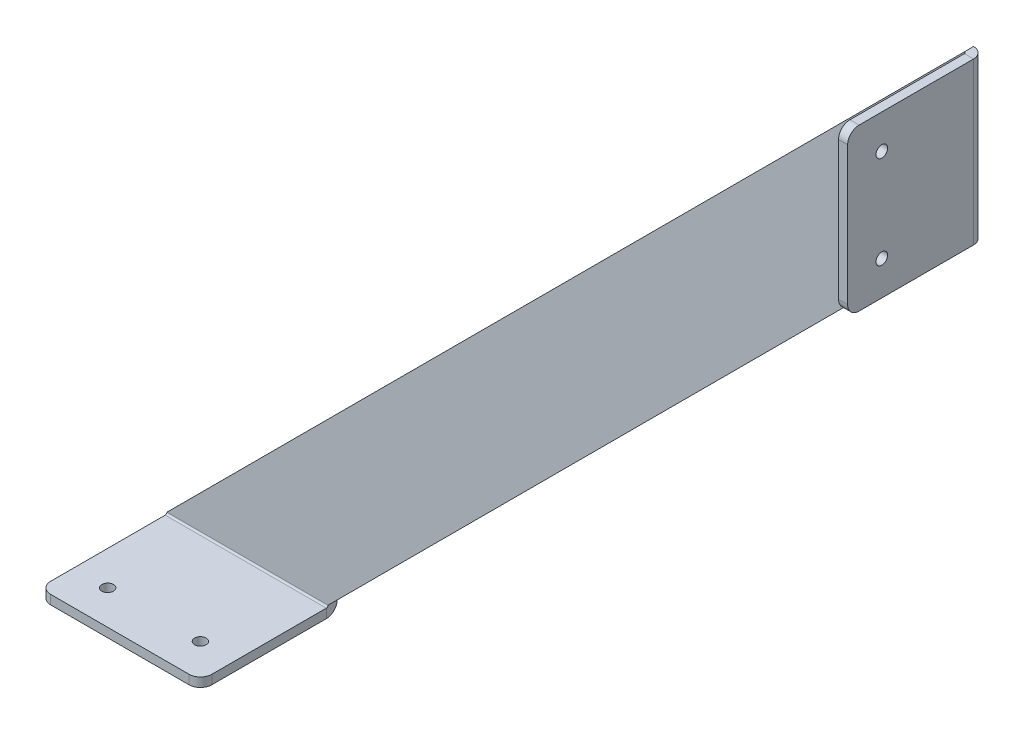
SolidWorks part; units mm, degrees
note: The reader was unsure of these and kept them because the rebuilt part matched: flange length of "Edge-Flange1".
material "AISI 304"
ref_plane "Front Plane" through (0, 0, 0) normal (0, 0, 1) x (1, 0, 0)
ref_plane "Top Plane" through (0, 0, 0) normal (0, 1, 0) x (1, 0, 0)
ref_plane "Right Plane" through (0, 0, 0) normal (1, 0, 0) x (0, 0, -1)
sketch "Sketch1" plane through (0, 0, 0) normal (0, 0, 1) x (1, 0, 0)
  line L0 (175, 175) -> (-175, -175)
  line L1 (-175, -175) -> (175, -175) construction
  line L2 (-175, -175) -> (-175, 175) construction
  line L3 (-175, 175) -> (175, 175) construction
  line L4 (175, -175) -> (175, 175) construction
  line L5 (-175, -175) -> (175, 175) construction
  line L6 (-175, 175) -> (175, -175) construction
  line L7 (-175, -175) -> (-104.2893, -175)
  line L8 (-104.2893, -175) -> (175, 104.2893)
  line L9 (175, 104.2893) -> (175, 175)
  point P0 (0, 0)
  dimension "Lateral" = 350
  dimension "D3" = 50
sheet metal parameters "Sheet-Metal1" thickness 4 parameters "D1"=0.7366
base flange "Base-Flange1" sketch "Sketch1" thickness 4 reverse thickness direction no parameters "D1"=0.7366
edge flange "Edge-Flange1" sketch "Sketch8" flange profiles "Sketch8", "Sketch9" flange angle 90 flange length 60 flange position bend outside bend radius 0.7366 thickness 4 parameters "D6"=10, "D8"=1
sketch "Sketch8" plane through (175, 0, 0) normal (1, 0, 0) x (0, 1, 0)
  line L2 (104.2893, 0) -> (104.2893, 56)
  line L3 (104.2893, 56) -> (175, 56)
  line L4 (175, 56) -> (175, 0)
  line L5 (104.2893, 0) -> (175, 0) construction
  line L6 (104.2893, 0) -> (175, 0)
sketch "Sketch9" plane through (0, -175, 0) normal (0, -1, 0) x (1, 0, 0)
  line L0 (-175, 0) -> (-104.2893, 0) construction
  line L1 (-175, 0) -> (-104.2893, 0)
  line L2 (-175, 0) -> (-175, 56)
  line L3 (-175, 56) -> (-104.2893, 56)
  line L4 (-104.2893, 56) -> (-104.2893, 0)
bend "EdgeBend1" bend radius 0.7366 bend angle 90 parameters "D5"=1
bend "EdgeBend2" bend radius 0.7366 bend angle 90 parameters "D5"=2
sketch "Sketch13" plane through (179.7366, 0, 0) normal (1, 0, 0) x (0, 0, -1)
  line L0 (4, 104.2893) -> (4, 175) construction
  line L4 (-0.7366, 175) -> (-56, 175) construction
  line L5 (-28, 175) -> (-28, 104.2893) construction
  line L6 (-56, 104.2893) -> (-0.7366, 104.2893) construction
  line L7 (-56, 175) -> (-56, 104.2893) construction
  line L10 (-41, 175) -> (-41, 104.2893) construction
  line L11 (-56, 139.6447) -> (27.4411, 139.6447) construction
  circle A0 centre (-41, 160) radius 2.55
  circle A1 centre (-41, 119.2893) radius 2.55
  dimension "D3" = 5.1
  dimension "D1" = 28
  dimension "D2" = 45
  dimension "D5" = 15
extrude "Cut-Extrude1" cut sketch "Sketch13" against normal up to surface (4 mm away) up to face at (175.7366, 139.6447, 28.3683)
sketch "Sketch14" plane through (0, -179.7366, 0) normal (0, -1, 0) x (1, 0, 0)
  line L0 (-104.2893, 41) -> (-175, 41) construction
  line L1 (-104.2893, 56) -> (-104.2893, 0) construction
  line L2 (-175, 56) -> (-175, 0.7366) construction
  line L3 (-104.2893, 56) -> (-175, 56) construction
  line L4 (-139.6447, 56) -> (-139.6447, -9.1129) construction
  line L5 (-104.2893, 0.7366) -> (-104.2893, 56) construction
  line L6 (-175, -4) -> (-104.2893, -4) construction
  circle A0 centre (-119.2893, 41) radius 2.55
  circle A1 centre (-160, 41) radius 2.55
  dimension "D2" = 5.1
  dimension "D3" = 15
  dimension "D1" = 45
extrude "Cut-Extrude2" cut sketch "Sketch14" against normal up to surface (4 mm away) up to face at (-139.6447, -175.7366, 28.3683)
fillet "Fillet1" radius 5 4 edges at (177.7366, 104.2893, 56) (177.7366, 175, 56) (-104.2893, -177.7366, 56) (-175, -177.7366, 56)
flat pattern "Flat-Pattern1" [suppressed]
sketch "Bend-Lines1" plane through (0, 0, 0) normal (0, 1, 0) x (1, 0, 0)
sketch3d "Bounding-Box1" [suppressed]
  line L0 (139.6447, -210.3553, 0) -> (-210.3553, 139.6447, 0) construction
  line L1 (175, -175, 0) -> (-175, 175, 0) construction
  line L2 (139.6447, -210.3553, 0) -> (175, -175, 0) construction
  line L3 (-210.3553, 139.6447, 0) -> (-175, 175, 0) construction
bend of the flat pattern "Flatten-<EdgeBend1>1"
bend of the flat pattern "Flatten-<EdgeBend2>1"
